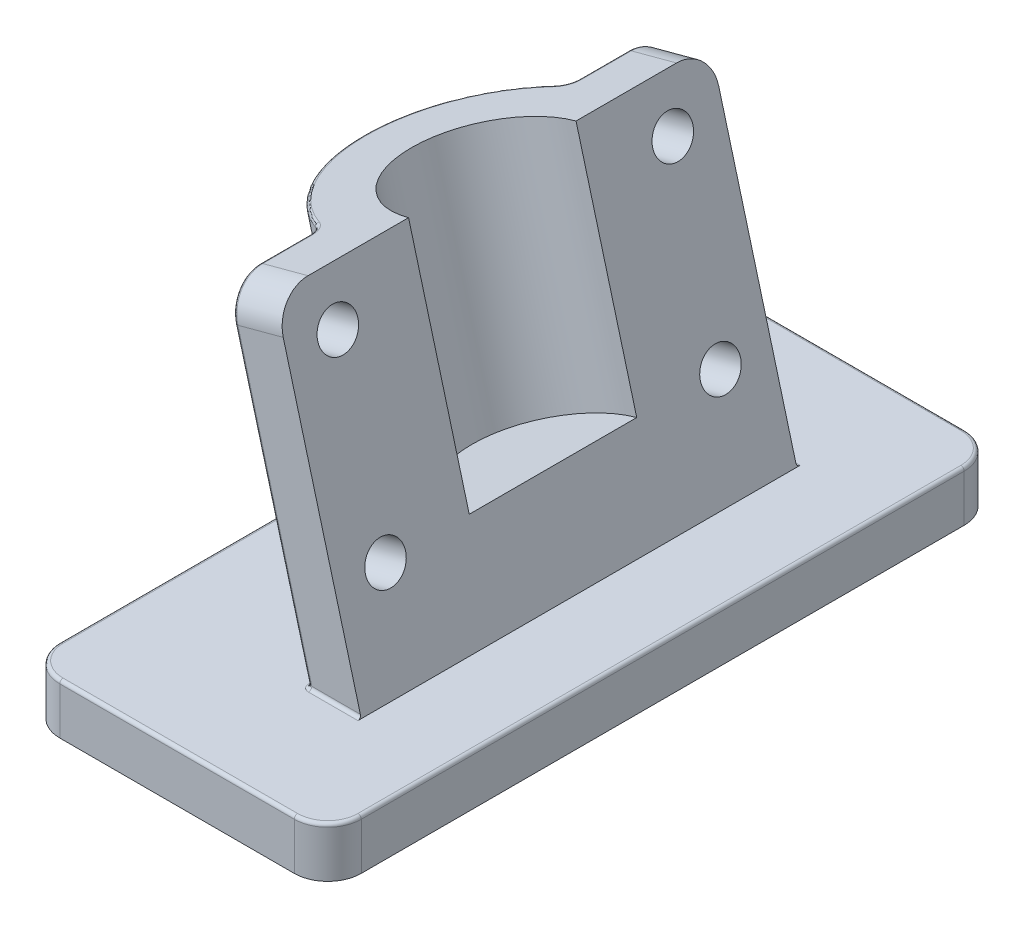
SolidWorks part; units mm, degrees
ref_plane "Front Plane" through (0, 0, 0) normal (0, 0, 1) x (1, 0, 0)
ref_plane "Top Plane" through (0, 0, 0) normal (0, 1, 0) x (1, 0, 0)
ref_plane "Right Plane" through (0, 0, 0) normal (1, 0, 0) x (0, 0, -1)
sketch "Sketch1" plane through (0, 0, 0) normal (0, 1, 0) x (1, 0, 0)
  line L1 (0, 0) -> (90, 0)
  line L2 (0, 0) -> (0, 200)
  line L3 (0, 200) -> (90, 200)
  line L4 (90, 0) -> (90, 200)
  dimension "D1" = 90
  dimension "D2" = 200
extrude "Boss-Extrude1" add sketch "Sketch1" along normal blind 15
sketch "Sketch2" plane through (0, 15, 0) normal (0, 1, 0) x (1, 0, 0)
  line L0 (0, 35) -> (90, 35) construction
  line L1 (0, 200) -> (0, 0) construction
  line L2 (65, 0) -> (65, 200) construction
  line L3 (0, 0) -> (90, 0) construction
  line L4 (90, 0) -> (90, 200) construction
  line L5 (90, 200) -> (0, 200) construction
  dimension "D1" = 35
  dimension "D2" = 25
ref_plane "Plane1" through (64.3958, 17.2548, 0) normal (0.9659, 0.2588, 0) x (0.2588, -0.9659, 0)
sketch "Sketch3" plane through (64.3958, 17.2548, 0) normal (0.9659, 0.2588, 0) x (0.2588, -0.9659, 0)
  line L0 (2.3344, 35) -> (-97.6656, 35) construction
  line L1 (-14.4889, 35) -> (8.8048, 35) construction
  line L2 (2.3344, 0) -> (2.3344, 200) construction
  dimension "D1" = 100
ref_plane "Plane2" through (39.1181, 111.5926, -35) normal (-0.2588, 0.9659, 0) x (0.9659, 0.2588, 0)
sketch "Sketch4" plane through (39.1181, 111.5926, -35) normal (-0.2588, 0.9659, 0) x (0.9659, 0.2588, 0)
  line L0 (0, 0) -> (0, 40)
  line L1 (0, 90) -> (0, 130)
  line L2 (0, -35) -> (0, 165) construction
  arc A0 (0, 90) -> (0, 40) centre (0, 65) ccw
  dimension "D2" = 25
  dimension "D1" = 130
extrude "Extrude-Thin1" add sketch "Sketch4" against normal up to next thin thin type one direction reverse wall 15
fillet "Fillet1" radius 10 6 edges at (90, 7.5, 0) (90, 7.5, -200) (0, 7.5, -200) (0, 7.5, 0) (31.8737, 109.6514, -165) (31.8737, 109.6514, -35)
hole_wizard "Ø12.0 (12) Diameter Hole1" positions "Sketch6" profile "Sketch5" hole size "Ø12.0" standard "ANSI Metric" end condition through all
sketch "Sketch6" plane through (64.3958, 17.2548, 0) normal (0.9659, 0.2588, 0) x (0, 0, -1)
  line L0 (125, 97.6656) -> (155, 97.6656) construction
  line L1 (100, 147.9346) -> (100, 68.8184) construction
  line L2 (100, 27.1135) -> (100, 104.1737) construction
  point P0 (50, 82.6656)
  point P2 (50, 27.6656)
  point P4 (150, 82.6656)
  point P6 (150, 27.6656)
  dimension "D1" = 15
  dimension "D2" = 55
  dimension "D3" = 100
sketch "Sketch5" plane through (43.0004, 97.1037, -50) normal (0, 0, 1) x (-0.2588, 0.9659, 0)
  line L0 (0, 0) -> (0, 66.6675)
  line L1 (0, 66.6675) -> (6, 66.6675)
  line L2 (6, 66.6675) -> (6, 0)
  line L5 (6, 0) -> (0, 0)
  line L11 (0, -6.35) -> (0, 107.95) construction
  dimension "Thru Hole Dia." = 12
  dimension "Thru Hole Depth" = 66.6675
ref_plane "Plane3" through (-7.1604, 26.723, 0) normal (-0.2588, 0.9659, 0) x (0.9659, 0.2588, 0)
sketch "Sketch7" plane through (-7.1604, 26.723, 0) normal (-0.2588, 0.9659, 0) x (0.9659, 0.2588, 0)
  line L0 (66.6675, 75) -> (66.6675, 125)
  arc A0 (66.6675, 125) -> (66.6675, 75) centre (66.6675, 100) ccw construction
  arc A1 (66.6675, 125) -> (66.6675, 75) centre (66.6675, 100) ccw
extrude "Boss-Extrude2" add sketch "Sketch7" against normal up to next
fillet "Fillet4" radius 5 2 edges at (37.05, 61.3551, -137.081) (37.05, 61.3551, -62.919)
fillet "Fillet2" radius 1 9 edges at (0.4811, 101.2398, -100) (24.6292, 107.7103, -147.6556) (25.3873, 104.8812, -162.0711) (24.6292, 107.7103, -52.3444) (25.3873, 104.8812, -37.9289) (38.3441, 56.5255, -165) (38.3441, 56.5255, -35) (23.904, 107.516, -137.6761) (23.904, 107.516, -62.3239)
fillet "Fillet3" radius 1 17 edges at (49.4709, 15, -152.1556) (23.589, 15, -100) (87.0711, 15, -197.0711) (90, 15, -100) (87.0711, 15, -2.9289) (45, 15, 0) (2.9289, 15, -2.9289) (0, 15, -100) (2.9289, 15, -197.0711) (49.4709, 15, -47.8444) (45, 15, -200) (57.7531, 15, -35) (49.7741, 15, -35.2929) (57.7531, 15, -165) (49.7741, 15, -164.7071) (48.6936, 15, -137.6761) (48.6936, 15, -62.3239)
